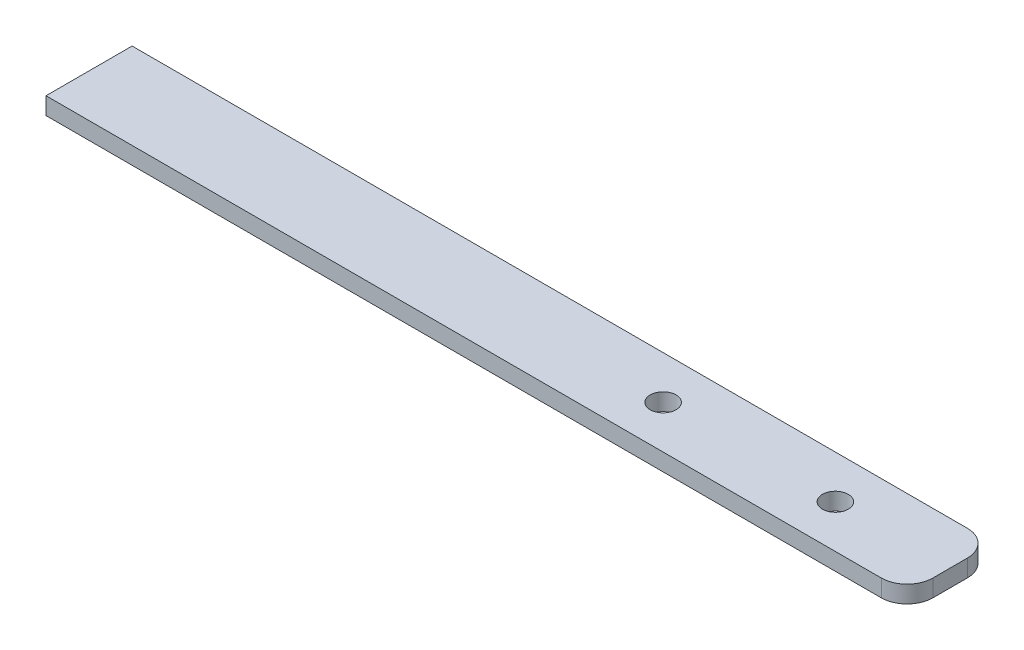
SolidWorks part; units mm, degrees
ref_plane "Front Plane" through (0, 0, 0) normal (0, 0, 1) x (1, 0, 0)
ref_plane "Top Plane" through (0, 0, 0) normal (0, 1, 0) x (1, 0, 0)
ref_plane "Right Plane" through (0, 0, 0) normal (1, 0, 0) x (0, 0, -1)
sketch "Sketch1" plane through (0, 0, 0) normal (0, 1, 0) x (1, 0, 0)
  line L1 (-50, 5) -> (50, 5)
  line L2 (-50, 5) -> (-50, -5)
  line L3 (-50, -5) -> (50, -5)
  line L4 (50, 5) -> (50, -5)
  line L5 (-50, 5) -> (50, -5) construction
  line L6 (-50, -5) -> (50, 5) construction
  point P0 (0, 0)
  dimension "D1" = 10
  dimension "D2" = 100
extrude "Boss-Extrude1" add sketch "Sketch1" along normal blind 2
sketch "Sketch2" plane through (0, 2, 0) normal (0, 1, 0) x (1, 0, 0)
  line L0 (26.3156, 5) -> (26.3156, -5) construction
  line L1 (-50, -5) -> (50, -5) construction
  point P10 (26.3156, 0)
fillet "Fillet1" radius 3 2 edges at (50, 1, 5) (50, 1, -5)
hole_wizard "Ø3.0mm Dowel Hole1" positions "Sketch3" profile "Sketch5" hole size "Ø3.0" standard "ISO" end condition through all
sketch "Sketch3" plane through (0, 2, 0) normal (0, 1, 0) x (1, 0, 0)
  point P0 (36.6695, 0)
  point P5 (16.6695, 0)
  dimension "D1" = 20
sketch "Sketch5" plane through (36.6695, 2, 0) normal (1, 0, 0) x (0, 0, 1)
  line L0 (0, 0) -> (0, 2)
  line L1 (0, 2) -> (1.5, 2)
  line L2 (1.5, 2) -> (1.5, 0)
  line L5 (1.5, 0) -> (0, 0)
  line L11 (0, -22.0399) -> (0, 107.95) construction
  dimension "Thru Hole Dia." = 3
  dimension "Thru Hole Depth" = 2
